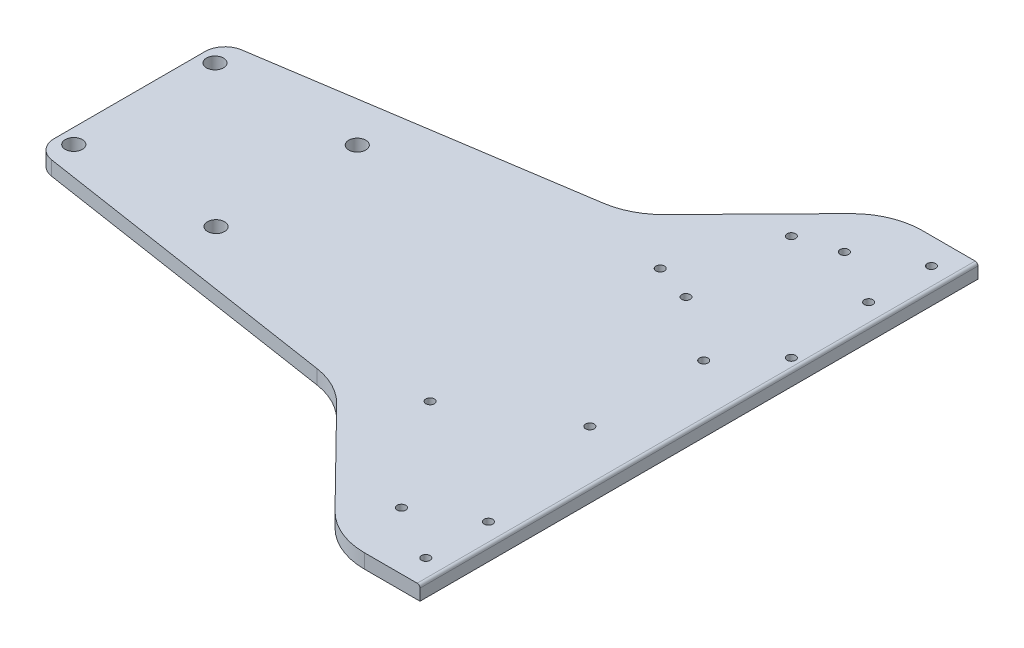
SolidWorks part; units mm, degrees
material "Plastique personnalisé"
ref_plane "Plan de face" through (0, 0, 0) normal (0, 0, 1) x (1, 0, 0)
ref_plane "Plan de dessus" through (0, 0, 0) normal (0, 1, 0) x (1, 0, 0)
ref_plane "Plan de droite" through (0, 0, 0) normal (1, 0, 0) x (0, 0, -1)
sketch "Esquisse1" plane through (0, 0, 0) normal (0, 1, 0) x (1, 0, 0)
  line L0 (0, 0) -> (200, 0) construction
  line L1 (200, -98) -> (200, 98) construction
  line L2 (0, -32.5) -> (0, 32.5) construction
  line L4 (200, 98) -> (180.4869, 98)
  line L5 (162.6514, 90.5184) -> (130.2275, 57.5077)
  line L6 (0, 19.6247) -> (0, -19.6247)
  line L7 (200, 98) -> (200, -98)
  line L8 (200, -98) -> (180.4869, -98)
  line L9 (162.6514, -90.5184) -> (130.2275, -57.5077)
  line L11 (116.1812, -50.3149) -> (0, -32.5)
  line L12 (0, -19.6247) -> (0, -32.5)
  line L13 (116.1812, 50.3149) -> (0, 32.5)
  line L14 (0, 32.5) -> (0, 19.6247)
  arc A0 (116.1812, 50.3149) -> (130.2275, 57.5077) centre (112.392, 75.0261) ccw
  arc A1 (180.4869, 98) -> (162.6514, 90.5184) centre (180.4869, 73) ccw
  arc A3 (180.4869, -98) -> (162.6514, -90.5184) centre (180.4869, -73) cw
  arc A4 (116.1812, -50.3149) -> (130.2275, -57.5077) centre (112.392, -75.0261) cw
  point P13 (170, 98)
  dimension "D5" = 25
  dimension "D1" = 200
  dimension "D2" = 98
  dimension "D3" = 32.5
  dimension "D4" = 30
extrude "Boss.-Extru.1" add sketch "Esquisse1" along normal blind 5
fillet "Congé3" radius 7 2 edges at (0, 2.5, 32.5) (0, 2.5, -32.5)
sketch "Esquisse3" plane through (0, 5, 0) normal (0, 1, 0) x (1, 0, 0)
  circle A0 centre (5.2281, -24.8573) radius 3
  circle A1 centre (5.2281, 24.7436) radius 3
  circle A2 centre (55.2084, -24.8573) radius 3
  circle A3 centre (55.2084, 24.7436) radius 3
  dimension "D1" = 6
  dimension "D2" = 6
  dimension "D3" = 6
  dimension "D4" = 6
extrude "Enlèv. mat.-Extru.1" cut sketch "Esquisse3" against normal blind 5
fillet "Congé2" radius 1 1 edges at (200, 5, 0)
sketch "Esquisse2" plane through (0, 5, 0) normal (0, 1, 0) x (1, 0, 0)
  line L0 (199, 0) -> (-35.8, 0) construction
  line L1 (199, -98) -> (199, 98) construction
ref_axis "Axe1" through (199, 5, 0) along (-1, 0, 0)
sketch "Esquisse4" plane through (0, 5, 0) normal (0, 1, 0) x (1, 0, 0)
  line L0 (199, 0) -> (-81.2291, 0) construction
  circle A0 centre (192.8013, -66.778) radius 1.5038
  circle A1 centre (192.8246, -88.8048) radius 1.4981
  circle A2 centre (173.2691, -77.7914) radius 1.5032
  circle A4 centre (173.2691, 77.7914) radius 1.5032
  circle A5 centre (192.8246, 88.8048) radius 1.4981
  circle A6 centre (192.8013, 66.778) radius 1.5038
extrude "Enlèv. mat.-Extru.2" cut sketch "Esquisse4" against normal blind 10
sketch "Esquisse5" plane through (0, 5, 0) normal (0, 1, 0) x (1, 0, 0)
  line L0 (197.583, 0.0601) -> (146.7238, 0) construction
  line L1 (199, 0) -> (-35.8, 0) construction
  line L2 (181.583, 20.0601) -> (181.6303, -19.9777) construction
  circle A0 centre (181.583, 20.0601) radius 12.3747
  circle A1 centre (223.583, 0.0601) radius 26 construction
  circle A2 centre (181.6303, -19.9777) radius 12.3747
  dimension "D1" = 24.7495
  dimension "D2" = 40.0377
sketch "Esquisse6" plane through (0, 5, 0) normal (0, 1, 0) x (1, 0, 0)
  circle A0 centre (181.583, 20.0601) radius 1.5
  circle A1 centre (181.6303, -19.9777) radius 1.5
extrude "Enlèv. mat.-Extru.3" cut sketch "Esquisse6" against normal blind 10
sketch "Esquisse7" plane through (0, 5, 0) normal (0, 1, 0) x (1, 0, 0)
  line L0 (-17.0668, 0) -> (188.0366, 0) construction
  line L1 (199, 0) -> (-35.8, 0) construction
  circle A0 centre (145.9493, 40.4145) radius 1.5
  circle A1 centre (145.9493, -40.4145) radius 1.5
extrude "Enlèv. mat.-Extru.4" cut sketch "Esquisse7" against normal blind 10
sketch "Esquisse8" plane through (0, 5, 0) normal (0, 1, 0) x (1, 0, 0)
  circle A0 centre (196.1489, 36.2746) radius 1.5
  circle A2 centre (159.1489, 73.2746) radius 1.5
  circle A3 centre (159.1489, 36.2746) radius 1.5
extrude "Enlèv. mat.-Extru.5" cut sketch "Esquisse8" against normal blind 10
